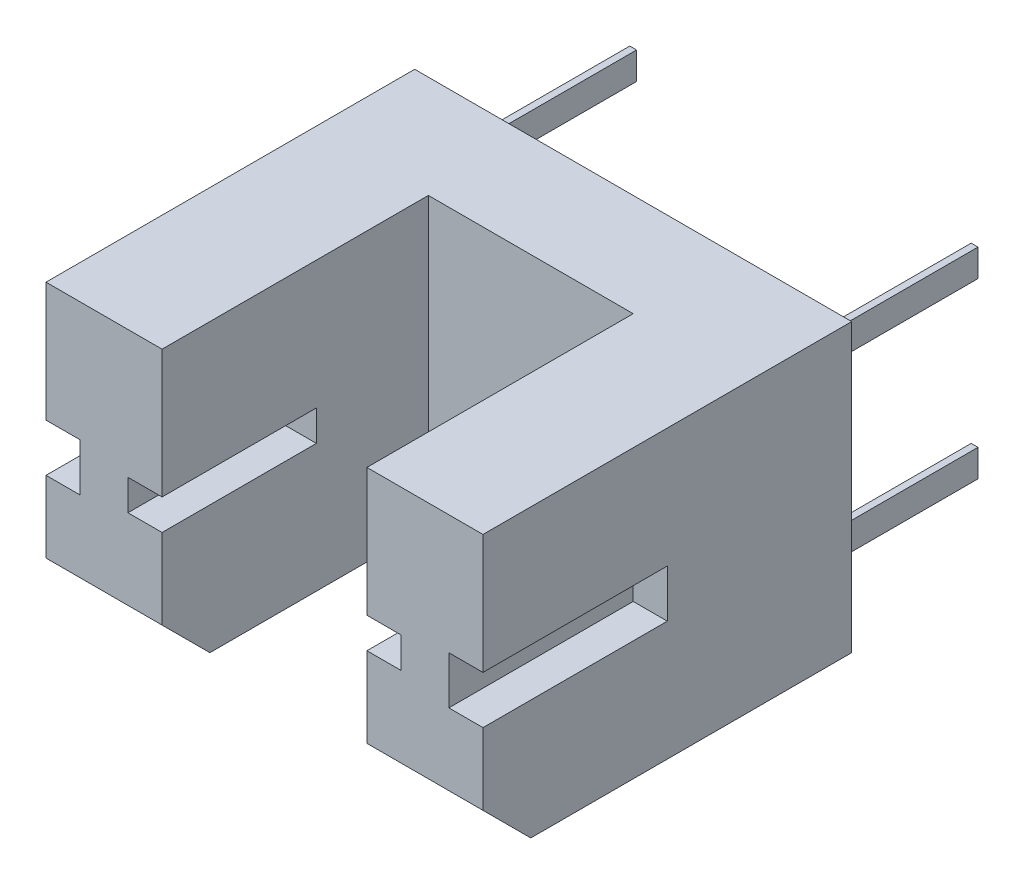
SolidWorks part; units mm, degrees
ref_plane "Front" through (0, 0, 0) normal (0, 0, 1) x (1, 0, 0)
ref_plane "Top" through (0, 0, 0) normal (0, 1, 0) x (1, 0, 0)
ref_plane "Right" through (0, 0, 0) normal (1, 0, 0) x (0, 0, -1)
sketch "Эскиз1" plane through (0, 0, 0) normal (0, 1, 0) x (1, 0, 0)
  line L0 (3.2, 0) -> (-3.2, 0)
  line L1 (3.2, 0) -> (3.2, -5.4)
  line L2 (3.2, -5.4) -> (1.5, -5.4)
  line L3 (1.5, -5.4) -> (1.5, -1.5)
  line L4 (1.5, -1.5) -> (-1.5, -1.5)
  line L5 (-1.5, -1.5) -> (-1.5, -5.4)
  line L6 (-1.5, -5.4) -> (-3.2, -5.4)
  line L8 (-3.2, 0) -> (-3.2, -5.4)
  line L9 (0, 0) -> (0, -1.5) construction
  dimension "D1" = 6.4
  dimension "D2" = 5.4
  dimension "D3" = 3
  dimension "D4" = 1.5
extrude "Бобышка-Вытянуть1" add sketch "Эскиз1" along normal blind 2.1 and the other way blind 2.1
sketch "Эскиз3" plane through (3.2, 0, 0) normal (1, 0, 0) x (0, 0, -1)
  line L0 (-5.4, -2.1) -> (-5.4, 2.1) construction
  line L1 (-5.4, -0.35) -> (-2.7, -0.35)
  line L2 (-5.4, -0.35) -> (-5.4, 0.35)
  line L3 (-5.4, 0.35) -> (-2.7, 0.35)
  line L4 (-2.7, -0.35) -> (-2.7, 0.35)
  line L5 (-5.4, -0.35) -> (-2.7, 0.35) construction
  line L6 (-5.4, 0.35) -> (-2.7, -0.35) construction
  line L7 (-5.4, 0) -> (-4.05, 0) construction
  point P4 (-4.05, 0)
  dimension "D1" = 0.7
  dimension "D2" = 2.7
extrude "Вырез-Вытянуть1" cut sketch "Эскиз3" against normal blind 0.5 contours L3 L4 L1 L2
sketch "Эскиз4" plane through (1.5, 0, 0) normal (-1, 0, 0) x (0, 0, 1)
  line L0 (5.4, -2.1) -> (5.4, 2.1) construction
  line L1 (3.14, 0.225) -> (5.4, 0.225)
  line L2 (3.14, 0.225) -> (3.14, -0.225)
  line L3 (3.14, -0.225) -> (5.4, -0.225)
  line L4 (5.4, 0.225) -> (5.4, -0.225)
  line L5 (3.14, 0.225) -> (5.4, -0.225) construction
  line L6 (3.14, -0.225) -> (5.4, 0.225) construction
  line L7 (0, 0) -> (4.27, 0) construction
  point P4 (4.27, 0)
  dimension "D1" = 0.45
  dimension "D2" = 2.26
extrude "Вырез-Вытянуть2" cut sketch "Эскиз4" against normal blind 0.5
mirror "Зеркальное отражение1" about plane through (0, 0, 0) normal (1, 0, 0) of "Вырез-Вытянуть2", "Вырез-Вытянуть1"
chamfer "Фаска1" distance 0.7 angle 45 2 edges at (-2.35, -2.1, 5.4) (2.35, -2.1, 5.4)
sketch "Эскиз6" plane through (0, 0, 0) normal (0, 0, -1) x (-1, 0, 0)
  line L0 (2.9, -1.6) -> (2.9, 1.6)
  line L1 (2.9, 1.6) -> (1.9, 1.6)
  line L2 (1.9, 1.6) -> (1.9, 0.8)
  line L3 (1.9, 0.8) -> (1.5, 0.8)
  line L4 (1.5, 0.8) -> (1.5, 1.6)
  line L5 (1.5, 1.6) -> (-1.5, 1.6) construction
  line L6 (-1.5, 1.6) -> (-1.5, 0.8)
  line L7 (-1.5, 0.8) -> (-1.9, 0.8)
  line L8 (-1.9, 0.8) -> (-1.9, 1.6)
  line L9 (-1.9, 1.6) -> (-2.9, 1.6)
  line L10 (-2.9, 1.6) -> (-2.9, -1.6)
  line L11 (-2.9, -1.6) -> (-1.9, -1.6)
  line L12 (-1.9, -1.6) -> (-1.9, -0.8)
  line L13 (-1.9, -0.8) -> (-1.5, -0.8)
  line L14 (-1.5, -0.8) -> (-1.5, -1.6)
  line L15 (-1.5, -1.6) -> (1.5, -1.6) construction
  line L16 (1.5, -1.6) -> (1.5, -0.8)
  line L17 (1.5, -0.8) -> (1.9, -0.8)
  line L18 (1.9, -0.8) -> (1.9, -1.6)
  line L19 (1.9, -1.6) -> (2.9, -1.6)
  line L20 (0, 1.6) -> (0, -1.6) construction
  line L21 (-2.9, 0) -> (2.9, 0) construction
  line L22 (3.2, -2.1) -> (3.2, 2.1) construction
  line L24 (-1.5, 1.6) -> (-0.8292, 1.6)
  line L25 (1.5, 1.6) -> (0.8292, 1.6)
  line L26 (-1.5, -1.6) -> (-0.4873, -1.6)
  line L27 (1.5, -1.6) -> (0.4873, -1.6)
  line L28 (0, -1.25) -> (0, 1.25) construction
  arc A0 (0.8292, 1.6) -> (-0.8292, 1.6) centre (0, 1.25) cw
  arc A1 (-0.4873, -1.6) -> (0.4873, -1.6) centre (0, -1.25) cw
  point P22 (0, 0)
  point P26 (0, 0)
  point P33 (0, 0)
  dimension "D6" = 2.5
  dimension "D7" = 0.6
  dimension "D8" = 0.9
  dimension "D1" = 3.2
  dimension "D2" = 0.3
  dimension "D3" = 0.4
  dimension "D4" = 1
  dimension "D5" = 0.8
extrude "Вырез-Вытянуть3" cut sketch "Эскиз6" against normal blind 0.5
sketch "Эскиз5" plane through (0, 0, 0) normal (0, 0, -1) x (-1, 0, 0)
  line L0 (0, 1.25) -> (0, -1.25) construction
  line L1 (0.433, -1.5) -> (-0.433, -1.5)
  line L2 (0.4873, -1.6) -> (1.5, -1.6) construction
  line L3 (-0.6837, 1.4) -> (0.6837, 1.4)
  line L4 (1.5, 1.6) -> (0.8292, 1.6) construction
  circle A0 centre (0, -1.25) radius 0.5 construction
  circle A1 centre (0, 1.25) radius 0.7 construction
  arc A2 (0.433, -1.5) -> (-0.433, -1.5) centre (0, -1.25) ccw
  arc A3 (0.6837, 1.4) -> (-0.6837, 1.4) centre (0, 1.25) cw
  point P4 (0, 0)
  dimension "D1" = 1
  dimension "D2" = 1.4
  dimension "D4" = 0.1
  dimension "D5" = 0.2
  dimension "D3" = 2.5
extrude "Бобышка-Вытянуть3" add sketch "Эскиз5" along normal blind 0.8
fillet "Скругление1" radius 0.2 2 edges at (0, 1.4, -0.8) (0, 0.55, -0.8)
fillet "Скругление2" radius 0.1 2 edges at (0, -1.5, -0.8) (0, -0.75, -0.8)
sketch "Эскиз2" plane through (0, 0, 0.5) normal (0, 0, -1) x (-1, 0, 0)
  line L1 (-2.55, 1.47) -> (-2.45, 1.47)
  line L2 (-2.55, 1.47) -> (-2.55, 1.07)
  line L3 (-2.55, 1.07) -> (-2.45, 1.07)
  line L4 (-2.45, 1.47) -> (-2.45, 1.07)
  line L5 (-2.55, 1.47) -> (-2.45, 1.07) construction
  line L6 (-2.55, 1.07) -> (-2.45, 1.47) construction
  line L18 (50, 0) -> (-50, 0) construction
  line L20 (-2.55, -1.07) -> (-2.45, -1.07)
  line L21 (-2.45, -1.47) -> (-2.45, -1.07)
  line L22 (-2.55, -1.47) -> (-2.45, -1.47)
  line L23 (-2.55, -1.47) -> (-2.55, -1.07)
  line L24 (0, 50) -> (0, -50) construction
  line L25 (2.55, -1.07) -> (2.45, -1.07)
  line L26 (2.55, -1.47) -> (2.45, -1.47)
  line L27 (2.45, -1.47) -> (2.45, -1.07)
  line L28 (2.55, -1.47) -> (2.55, -1.07)
  line L29 (2.55, 1.47) -> (2.55, 1.07)
  line L30 (2.55, 1.47) -> (2.45, 1.47)
  line L31 (2.45, 1.47) -> (2.45, 1.07)
  line L32 (2.55, 1.07) -> (2.45, 1.07)
  point P4 (-2.5, 1.27)
  dimension "D1" = 0.1
  dimension "D2" = 2.5
  dimension "D3" = 1.27
  dimension "D6" = 0.4
extrude "Бобышка-Вытянуть2" add sketch "Эскиз2" along direction (0, 0, -1) on the side of the normal offset from surface (3 mm away) 2.5 up to face at (0, -0.0125, 0) offset beyond the face yes
